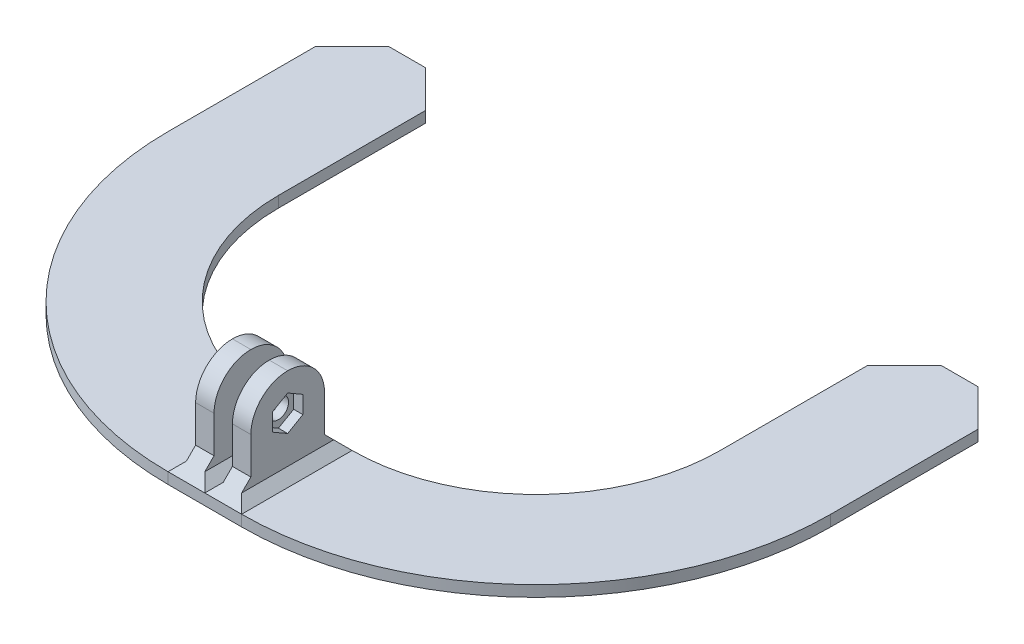
SolidWorks part; units mm, degrees
ref_plane "Front Plane" through (0, 0, 0) normal (0, 0, 1) x (1, 0, 0)
ref_plane "Top Plane" through (0, 0, 0) normal (0, 1, 0) x (1, 0, 0)
ref_plane "Right Plane" through (0, 0, 0) normal (1, 0, 0) x (0, 0, -1)
sketch "Sketch1" plane through (0, 0, 0) normal (0, 1, 0) x (1, 0, 0)
  line L0 (0, 15) -> (0, -15) construction
  line L1 (-10, 15) -> (10, 15)
  line L3 (-10, -15) -> (10, -15)
  line L5 (-10, 15) -> (-10, 65) construction
  line L6 (-10, 65) -> (-60, 65) construction
  line L7 (-60, 65) -> (-90, 65)
  line L8 (60, 65) -> (90, 65)
  arc A0 (-60, 65) -> (-10, 15) centre (-10, 65) ccw
  arc A1 (-90, 65) -> (-10, -15) centre (-10, 65) ccw
  arc A2 (60, 65) -> (10, 15) centre (10, 65) cw
  arc A3 (90, 65) -> (10, -15) centre (10, 65) cw
  dimension "D3" = 50
  dimension "D1" = 30
  dimension "D2" = 20
extrude "Boss-Extrude1" add sketch "Sketch1" along normal blind 3
sketch "Sketch4" plane through (0, 3, 0) normal (0, 1, 0) x (1, 0, 0)
  line L0 (0, 15) -> (0, -15) construction
  line L1 (10, 15) -> (-10, 15) construction
  line L2 (-10, -15) -> (10, -15) construction
  line L3 (-30, 0) -> (0, 0) construction
  line L4 (-2.5, 10) -> (-7.5, 10)
  line L5 (-2.5, 10) -> (-2.5, -10)
  line L6 (-2.5, -10) -> (-7.5, -10)
  line L7 (-7.5, 10) -> (-7.5, -10)
  line L9 (7.5, 10) -> (7.5, -10)
  line L10 (2.5, -10) -> (7.5, -10)
  line L11 (2.5, 10) -> (2.5, -10)
  line L12 (2.5, 10) -> (7.5, 10)
  point P15 (-2.5, 0)
  point P20 (0, 0)
  dimension "D1" = 5
  dimension "D2" = 2.5
  dimension "D3" = 20
extrude "Boss-Extrude2" add sketch "Sketch4" along normal blind 25
fillet "Fillet3" radius 10 4 edges at (5, 28, 10) (5, 28, -10) (-5, 28, -10) (-5, 28, 10)
sketch "Sketch5" plane through (-7.5, 0, 0) normal (-1, 0, 0) x (0, 0, 1)
  circle A0 centre (0, 18) radius 2.75
  arc A1 (10, 18) -> (0, 28) centre (0, 18) ccw construction
  dimension "D1" = 5.5
extrude "Cut-Extrude3" cut sketch "Sketch5" against normal through all both and the other way through all
sketch "Sketch6" plane through (7.5, 0, 0) normal (1, 0, 0) x (0, 0, -1)
  line L1 (0, 13.2369) -> (4.125, 15.6184)
  line L2 (4.125, 15.6184) -> (4.125, 20.3816)
  line L3 (4.125, 20.3816) -> (0, 22.7631)
  line L4 (0, 22.7631) -> (-4.125, 20.3816)
  line L5 (-4.125, 20.3816) -> (-4.125, 15.6184)
  line L6 (-4.125, 15.6184) -> (0, 13.2369)
  circle A0 centre (0, 18) radius 4.125 construction
  dimension "D1" = 8.25
extrude "Cut-Extrude4" cut sketch "Sketch6" against normal blind 2.5
chamfer "Chamfer1" distance 5 angle 45 4 edges at (5, 3, -10) (-5, 3, -10) (-5, 3, 10) (5, 3, 10)
chamfer "Chamfer3" distance 2.5 angle 45 4 edges at (-2.5, 3, 0) (2.5, 3, 0) (-7.5, 3, 0) (7.5, 3, 0)
sketch "Sketch7" plane through (0, 0, -65) normal (0, 0, -1) x (-1, 0, 0)
  line L0 (-90, 0) -> (-60, 0) construction
  line L1 (-60, 0) -> (-60, 3) construction
  line L2 (-60, 3) -> (-90, 3) construction
  line L3 (-90, 3) -> (-90, 0) construction
  line L4 (60, 0) -> (90, 0) construction
  line L5 (90, 0) -> (90, 3) construction
  line L6 (90, 3) -> (60, 3) construction
  line L7 (60, 3) -> (60, 0) construction
  line L8 (-90, 0) -> (-60, 0)
  line L9 (-60, 0) -> (-60, 3)
  line L10 (-60, 3) -> (-90, 3)
  line L11 (-90, 3) -> (-90, 0)
  line L12 (60, 0) -> (90, 0)
  line L13 (90, 0) -> (90, 3)
  line L14 (90, 3) -> (60, 3)
  line L15 (60, 3) -> (60, 0)
extrude "Boss-Extrude3" add sketch "Sketch7" along normal blind 50
chamfer "Chamfer4" distance 10 angle 45 4 edges at (90, 1.5, -115) (60, 1.5, -115) (-90, 1.5, -115) (-60, 1.5, -115)
